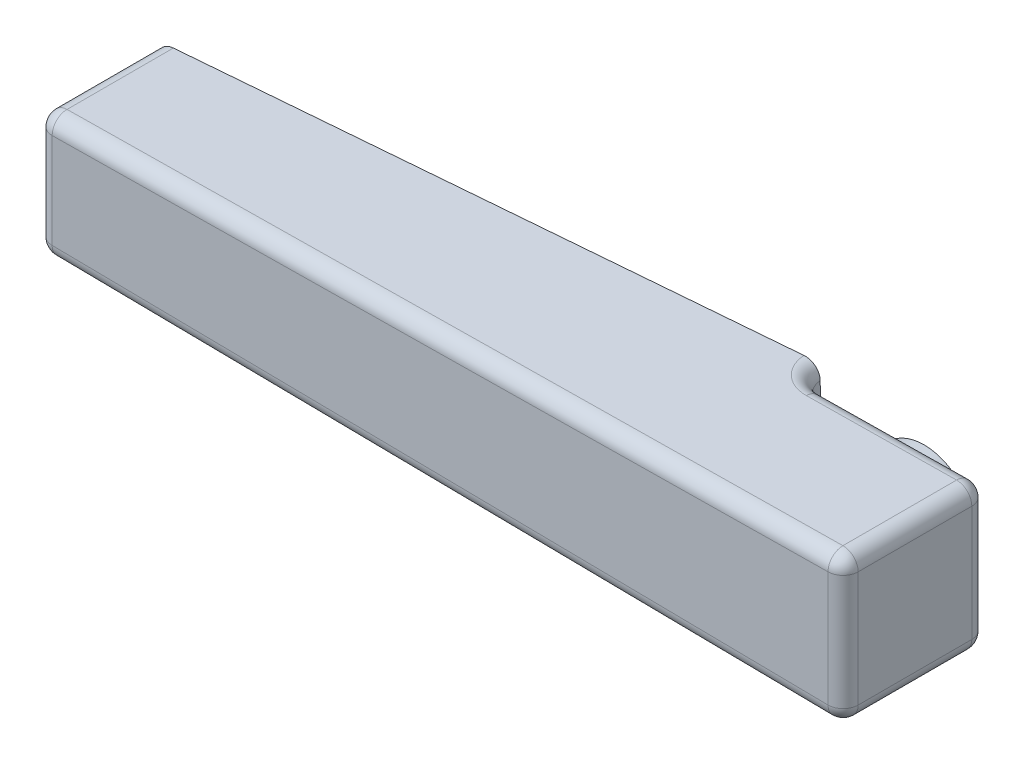
SolidWorks part; units mm, degrees
ref_plane "Front Plane" through (0, 0, 0) normal (0, 0, 1) x (1, 0, 0)
ref_plane "Top Plane" through (0, 0, 0) normal (0, 1, 0) x (1, 0, 0)
ref_plane "Right Plane" through (0, 0, 0) normal (1, 0, 0) x (0, 0, -1)
sketch "Sketch4" plane through (0, 0, 0) normal (0, 0, 1) x (1, 0, 0)
  line L0 (0, -41.5) -> (0, 41.5)
  line L1 (0, 41.5) -> (536, 48.5)
  line L2 (536, 48.5) -> (536, -48.5)
  line L3 (0, 0) -> (536, 0) construction
  line L4 (0, -41.5) -> (536, -48.5)
  dimension "D1" = 83
  dimension "D2" = 97
  dimension "D3" = 536
extrude "Boss-Extrude2" add sketch "Sketch4" along normal blind 109.94
sketch "Sketch7" plane through (-0.5419, 41.4929, 0) normal (-0.0131, 0.9999, 0) x (0.9999, 0.0131, 0)
  line L0 (-0.5419, -30) -> (426.5876, 0)
  line L3 (-0.5419, -109.94) -> (-0.5419, 0) construction
  line L4 (536.5876, 0) -> (0.5419, 0) construction
  line L5 (426.5876, 0) -> (-0.5419, 0)
  line L6 (-0.5419, 0) -> (-0.5419, -30)
  dimension "D1" = 79.94
  dimension "D2" = 110
extrude "Cut-Extrude3" cut sketch "Sketch7" against normal up to next
sketch "Sketch8" plane through (-0.5419, 41.4929, 0) normal (-0.0131, 0.9999, 0) x (0.9999, 0.0131, 0)
  line L0 (426.5876, 29.3977) -> (426.5876, -138.4635) construction
  line L1 (412.2335, 0) -> (536.5876, 0)
  line L2 (536.5876, -109.94) -> (536.5876, 0) construction
  line L3 (536.5876, -14.3541) -> (426.5876, -14.3541)
  line L4 (536.5876, 0) -> (536.5876, -14.3541)
  arc A0 (412.2335, 0) -> (426.5876, -14.3541) centre (426.5876, 0) ccw
  dimension "D1" = 110
extrude "Cut-Extrude4" cut sketch "Sketch8" against normal up to next
sketch "Sketch9" plane through (0, 0, 14.3541) normal (0, 0, -1) x (-1, 0, 0)
  line L0 (-426.8235, -15.2756) -> (-536, -15.2756) construction
  line L1 (-427.2389, -47.0796) -> (-426.0094, 47.0636) construction
  line L2 (-536, 48.5) -> (-536, -48.5) construction
  circle A0 centre (-464.2653, -15.2756) radius 33.1365
extrude "Boss-Extrude3" add sketch "Sketch9" along normal blind 30
sketch "Sketch10" plane through (2.0939, 0.0273, 29.8149) normal (-0.0701, -0.0009, -0.9975) x (-0.9975, 0.0001, 0.0701)
  line L0 (0, 0) -> (-411.2206, -0.0089) construction
  line L1 (-411.8344, -46.8935) -> (-410.6067, 46.8756) construction
  line L2 (7.7048, 41.3991) -> (7.6995, -41.6008) construction
  circle A0 centre (-55.2959, 29.9928) radius 3
  circle A1 centre (-110.2959, 29.9928) radius 3
  circle A2 centre (-165.2959, 29.9928) radius 3
  circle A3 centre (-220.2959, 29.9928) radius 3
  circle A4 centre (-275.2959, 29.9928) radius 3
  circle A5 centre (-330.2959, 29.9928) radius 3
  circle A6 centre (-55.2946, -29.9952) radius 3
  circle A7 centre (-110.2946, -29.9976) radius 3
  circle A8 centre (-165.2946, -30) radius 3
  circle A9 centre (-220.2946, -30.0024) radius 3
  circle A10 centre (-330.2946, -30.0072) radius 3
  circle A11 centre (-275.2946, -30.0048) radius 3
  point P27 (-330.2946, -30.0072)
  dimension "D4" = 6
  dimension "D2" = 63
  dimension "D3" = 60
  dimension "D1" = 6
extrude "Cut-Extrude5" cut sketch "Sketch10" against normal blind 20
fillet "Fillet1" radius 10 1 edges at (0, 41.5, 69.9319) type face fillet first side face at (317.8455, 45.651, 47.0562) second side face at (0, 0, 69.951)
fillet "Fillet2" radius 10 1 edges at (0, -41.5, 69.97) type face fillet first side face at (0, -4.9351, 69.9532) second side face at (354.6517, -46.1316, 38.8902)
fillet "Fillet3" radius 10 1 edges at (272.9347, 45.0644, 109.94) type face fillet first side face at (181.2725, 0, 109.94) second side face at (321.1353, 45.6939, 46.9407)
fillet "Fillet4" radius 10 1 edges at (536, 0, 109.94) type face fillet first side face at (536, 0, 75.4351) second side face at (273, 0, 109.94)
fillet "Fillet5" radius 10 1 edges at (536, 0, 14.3541) type face fillet first side face at (536, 0, 57.1471) second side face at (488.7136, -3.7145, 14.3541)
